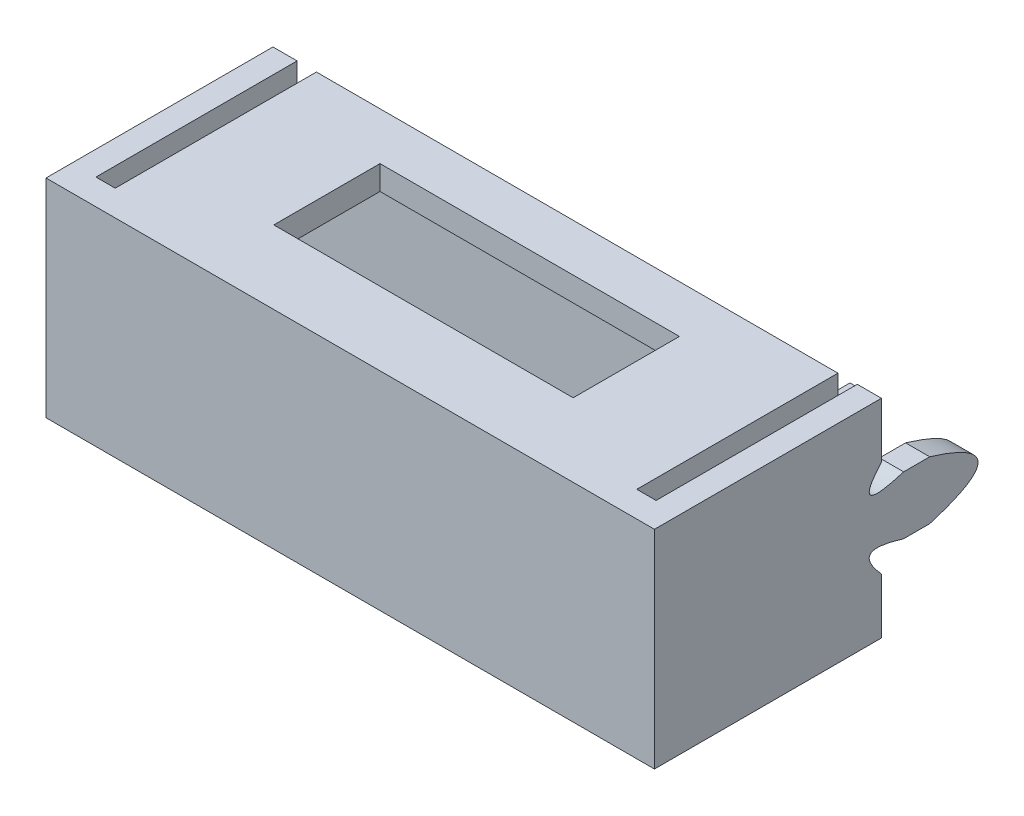
SolidWorks part; units mm, degrees
note: The reader was unsure of these and kept them because the rebuilt part matched: shared geometry of "草图10<2>".
ref_plane "前视基准面" through (0, 0, 0) normal (0, 0, 1) x (1, 0, 0)
ref_plane "上视基准面" through (0, 0, 0) normal (0, 1, 0) x (1, 0, 0)
ref_plane "右视基准面" through (0, 0, 0) normal (1, 0, 0) x (0, 0, -1)
sketch "草图1" plane through (0, 0, 0) normal (0, 0, 1) x (1, 0, 0)
  line L1 (-6.3, 2.15) -> (6.3, 2.15)
  line L2 (-6.3, 2.15) -> (-6.3, -2.15)
  line L3 (-6.3, -2.15) -> (6.3, -2.15)
  line L4 (6.3, 2.15) -> (6.3, -2.15)
  line L5 (-6.3, 2.15) -> (6.3, -2.15) construction
  line L6 (-6.3, -2.15) -> (6.3, 2.15) construction
  point P0 (0, 0)
extrude "拉伸-薄壁1" add sketch "草图1" along normal blind 4.7 thin
sketch "草图4" plane through (0, 0, 4.7) normal (0, 0, 1) x (1, 0, 0)
  line L1 (-5.8, 1.65) -> (5.8, 1.65)
  line L2 (-5.8, 1.65) -> (-5.8, -1.65)
  line L3 (-5.8, -1.65) -> (5.8, -1.65)
  line L4 (5.8, 1.65) -> (5.8, -1.65)
extrude "凸台-拉伸3" add sketch "草图4" against normal blind 0.5
sketch "草图6" plane through (0, -2.15, 0) normal (0, -1, 0) x (1, 0, 0)
  line L0 (-5.8, 0) -> (-5.8, 4.1663)
  line L1 (-5.8, 4.1663) -> (-5.4, 4.1663)
  line L2 (-5.4, 4.1663) -> (-5.4, 0)
  line L3 (-6.3, 0) -> (6.3, 0) construction
  line L4 (-5.4, 0) -> (-5.8, 0)
  line L5 (0, 4.7) -> (0, 0) construction
  line L6 (-6.3, 4.7) -> (6.3, 4.7) construction
  line L11 (-6.3, 4.7) -> (-6.3, 0) construction
  line L12 (5.4, 0) -> (5.8, 0)
  line L13 (5.4, 4.1663) -> (5.4, 0)
  line L14 (5.8, 4.1663) -> (5.4, 4.1663)
  line L15 (5.8, 0) -> (5.8, 4.1663)
  dimension "D1" = 0.5
extrude "切除-拉伸2" cut sketch "草图6" against normal through all
sketch "草图7" plane through (0, 0, 0) normal (0, 0, 1) x (1, 0, 0)
  line L5 (-6.4226, -2.3005) -> (6.4226, 2.3005) construction
  line L6 (-6.4226, 2.3005) -> (6.4226, -2.3005) construction
  line L7 (5.8, 1.65) -> (-5.8, 1.65)
  line L8 (5.8, 1.65) -> (5.8, -1.65)
  line L9 (5.8, -1.65) -> (-5.8, -1.65)
  line L10 (-5.8, 1.65) -> (-5.8, -1.65)
  point P0 (0, 0)
extrude "凸台-拉伸4" add sketch "草图7" along normal blind 0.8 and the other way blind 0.1 separate body
sketch "草图8" plane through (0, 0, -0.1) normal (0, 0, -1) x (-1, 0, 0)
  line L0 (6.3, 2.15) -> (6.3, -2.15) construction
  line L1 (3.75, 0.2) -> (4.25, 0.2)
  line L2 (3.75, 0.2) -> (3.75, -0.2)
  line L3 (3.75, -0.2) -> (4.25, -0.2)
  line L4 (4.25, 0.2) -> (4.25, -0.2)
  line L5 (3.75, 0.2) -> (4.25, -0.2) construction
  line L6 (3.75, -0.2) -> (4.25, 0.2) construction
  line L7 (1.75, 0.2) -> (2.25, 0.2)
  line L8 (1.75, 0.2) -> (1.75, -0.2)
  line L9 (1.75, -0.2) -> (2.25, -0.2)
  line L10 (2.25, 0.2) -> (2.25, -0.2)
  line L11 (1.75, 0.2) -> (2.25, -0.2) construction
  line L12 (1.75, -0.2) -> (2.25, 0.2) construction
  line L13 (-0.25, 0.2) -> (0.25, 0.2)
  line L14 (-0.25, 0.2) -> (-0.25, -0.2)
  line L15 (-0.25, -0.2) -> (0.25, -0.2)
  line L16 (0.25, 0.2) -> (0.25, -0.2)
  line L17 (-0.25, 0.2) -> (0.25, -0.2) construction
  line L18 (-0.25, -0.2) -> (0.25, 0.2) construction
  line L20 (0, 2.15) -> (0, -1.65) construction
  line L21 (-5.4, 2.15) -> (5.4, 2.15) construction
  line L22 (5.4, -1.65) -> (-5.4, -1.65) construction
  line L23 (-3.75, -0.2) -> (-4.25, 0.2) construction
  line L24 (-3.75, 0.2) -> (-4.25, -0.2) construction
  line L25 (-4.25, 0.2) -> (-4.25, -0.2)
  line L26 (-3.75, -0.2) -> (-4.25, -0.2)
  line L27 (-3.75, 0.2) -> (-3.75, -0.2)
  line L28 (-3.75, 0.2) -> (-4.25, 0.2)
  line L29 (-5.8, 0) -> (-5.8, 0.6)
  line L30 (-5.8, -2.15) -> (-5.8, 2.15) construction
  line L31 (-5.8, 0.6) -> (-6.3, 0.6)
  line L32 (-6.3, -2.15) -> (-6.3, 2.15) construction
  line L33 (-6.3, 0.6) -> (-6.3, -0.6)
  line L34 (-6.3, -0.6) -> (-5.8, -0.6)
  line L35 (-5.8, -0.6) -> (-5.8, 0)
  line L36 (5.8, -0.6) -> (5.8, 0)
  line L37 (6.3, -0.6) -> (5.8, -0.6)
  line L38 (6.3, 0.6) -> (6.3, -0.6)
  line L39 (5.8, 0.6) -> (6.3, 0.6)
  line L40 (5.8, 0) -> (5.8, 0.6)
  point P0 (4, 0)
  point P5 (2, 0)
  point P13 (0, 0)
  point P27 (-4, 0)
  dimension "D1" = 2.3
  dimension "D2" = 3
extrude "凸台-拉伸5" add sketch "草图8" along normal blind 2 from surface at -0.1 starting at face at (-6.05, 0, 0)
sketch "草图9" plane through (0, 2.15, 0) normal (0, 1, 0) x (1, 0, 0)
  line L0 (5.4, -4.1663) -> (5.4, 0) construction
  line L1 (-3.1, -0.9832) -> (3.1, -0.9832)
  line L2 (-3.1, -0.9832) -> (-3.1, -3.1832)
  line L3 (-3.1, -3.1832) -> (3.1, -3.1832)
  line L4 (3.1, -0.9832) -> (3.1, -3.1832)
  line L5 (-3.1, -0.9832) -> (3.1, -3.1832) construction
  line L6 (-3.1, -3.1832) -> (3.1, -0.9832) construction
  point P0 (0, -2.0832)
  point P10 (5.4, -2.0832)
extrude "切除-拉伸3" cut sketch "草图9" against normal blind 0.5 contours L4 L1 L2 L3
sketch "草图10" plane through (6.3, 0, 0) normal (1, 0, 0) x (0, 0, -1)
  line L0 (2, 0.6) -> (0, 0.6) construction
  line L1 (2, 0.6) -> (2, -0.6) construction
  line L2 (2, -0.6) -> (0, -0.6) construction
  line L3 (0, -2.15) -> (0, -0.6) construction
  line L4 (-0.8777, 0) -> (0.9955, 0) construction
  line L5 (0, 1.0003) -> (0.4603, 0.6)
  line L6 (0.4603, -0.6) -> (0, -1.0003)
  line L7 (1, 0.6) -> (4, 0.6)
  line L8 (4, 0.6) -> (4.2479, 0.6)
  line L9 (4.2479, 0.6) -> (4.2479, -0.6)
  line L10 (4.2479, -0.6) -> (1, -0.6)
  spline S0 degree 2 poles (1, 0.6) (3, 0) (1, -0.6) knots 0 0 0 1 1 1
  spline S1 degree 2 poles (0.4603, -0.6) (-0.6772, -0.249) (0, -1.0003) knots 0 0 0 1 1 1
  spline S2 degree 2 poles (0.4603, 0.6) (-0.6772, 0.249) (0, 1.0003) knots 0 0 0 1 1 1
extrude "切除-拉伸4" cut sketch "草图10" against normal blind 0.5
extrude "切除-拉伸5" cut sketch "草图10<2>" along normal blind 0.5 from surface
sketch "草图10<2>" plane through (6.3, 0, 0) normal (1, 0, 0) x (0, 0, -1) same geometry as "草图10"
chamfer "倒角1" distance 0.1 angle 45 16 edges at (-4.25, 0, -2) (-4, -0.2, -2) (-3.75, 0, -2) (-4, 0.2, -2) (-2.25, 0, -2) (-2, -0.2, -2) (-1.75, 0, -2) (-2, 0.2, -2) (-0.25, 0, -2) (0, -0.2, -2) (0.25, 0, -2) (0, 0.2, -2) (3.75, 0, -2) (4, -0.2, -2) (4.25, 0, -2) (4, 0.2, -2)
